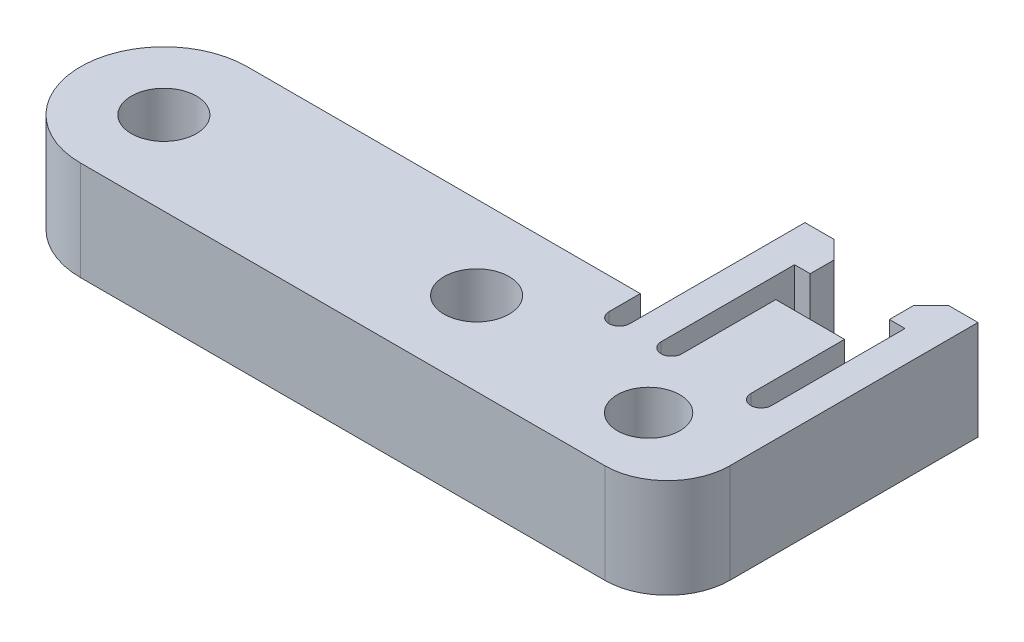
SolidWorks part; units mm, degrees
ref_plane "Front Plane" through (0, 0, 0) normal (0, 0, 1) x (1, 0, 0)
ref_plane "Top Plane" through (0, 0, 0) normal (0, 1, 0) x (1, 0, 0)
ref_plane "Right Plane" through (0, 0, 0) normal (1, 0, 0) x (0, 0, -1)
sketch "Sketch1" plane through (0, 0, 0) normal (0, 1, 0) x (1, 0, 0)
  line L1 (-1.65, 0) -> (1.65, 0)
  line L2 (-2.65, -5) -> (-2.65, 1.9)
  line L3 (-2.65, 1.9) -> (-1.9, 1.9)
  line L4 (2.65, -5) -> (2.65, 1.9)
  line L5 (-2.75, 3.9) -> (-4.15, 3.9)
  line L6 (-4.15, 3.9) -> (-4.15, -5)
  line L8 (2.75, 3.9) -> (4.15, 3.9)
  line L9 (4.15, 3.9) -> (4.15, -8)
  line L10 (1.9, 1.9) -> (2.65, 1.9)
  line L11 (1.15, -11) -> (-24, -11)
  line L12 (-5.15, -3) -> (-24, -3)
  line L13 (-4.15, -5) -> (-5.15, -5)
  line L14 (-2.65, -5) -> (-1.65, -5)
  line L15 (-1.65, 0) -> (-1.65, -5)
  line L16 (-5.15, -5) -> (-5.15, -3)
  line L17 (-1.9, 1.9) -> (-1.9, 3.05)
  line L18 (2.65, -5) -> (1.65, -5)
  line L19 (1.65, 0) -> (1.65, -5)
  line L20 (-1.9, 3.05) -> (-2.75, 3.9)
  line L21 (1.9, 1.9) -> (1.9, 3.05)
  line L22 (1.9, 3.05) -> (2.75, 3.9)
  arc A0 (4.15, -8) -> (1.15, -11) centre (1.15, -8) cw
  arc A2 (-24, -3) -> (-24, -11) centre (-24, -7) ccw
  circle A3 centre (-24, -7) radius 1.5625
  circle A4 centre (-9, -7) radius 1.5625
  dimension "D9" = 3.125
  dimension "D11" = 4
  dimension "D14" = 3
  dimension "D15" = 45
  dimension "D1" = 1.9
  dimension "D2" = 5.3
  dimension "D3" = 0.75
  dimension "D4" = 0.1
  dimension "D5" = 2
  dimension "D6" = 1.5
  dimension "D7" = 1
  dimension "D8" = 5
  dimension "D10" = 15
  dimension "D12" = 7
  dimension "D13" = 9
extrude "Boss-Extrude1" add sketch "Sketch1" along normal blind 4.7625
fillet "Fillet1" radius 0.5 6 edges at (-2.65, 2.3813, 5) (-1.65, 2.3813, 5) (2.65, 2.3813, 5) (1.65, 2.3813, 5) (-5.15, 2.3813, 5) (-4.15, 2.3813, 5)
sketch "Sketch2" plane through (0, 4.7625, 0) normal (0, 1, 0) x (1, 0, 0)
  line L0 (1.65, 0) -> (-1.65, 0) construction
  circle A0 centre (0, -7.75) radius 1.5
  dimension "D1" = 3
  dimension "D2" = 7.75
extrude "Cut-Extrude1" cut sketch "Sketch2" against normal through all
